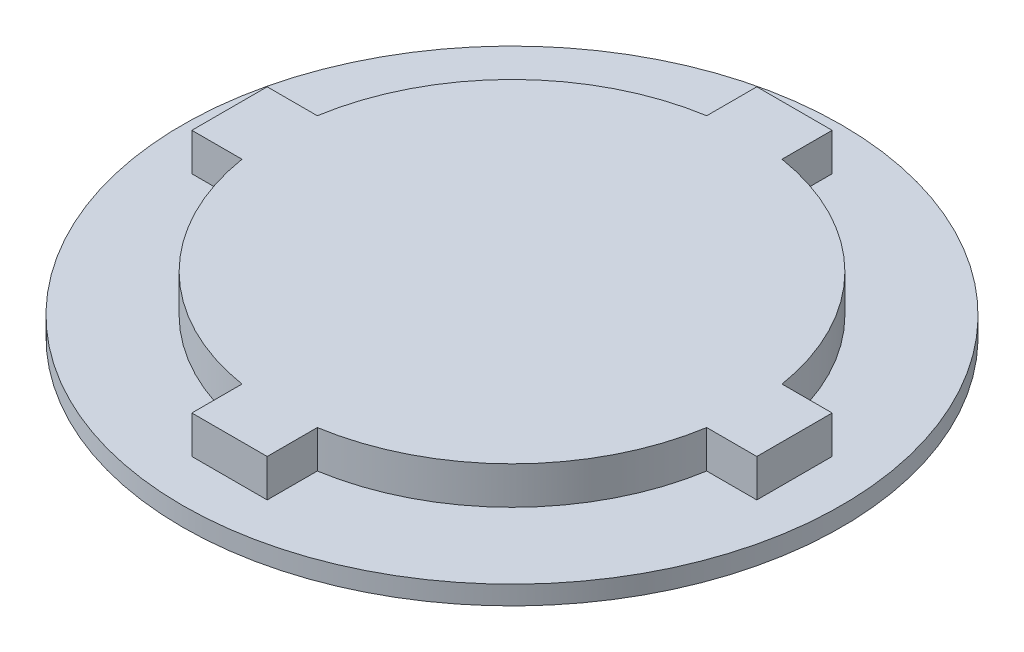
SolidWorks part; units mm, degrees
ref_plane "Alzado" through (0, 0, 0) normal (0, 0, 1) x (1, 0, 0)
ref_plane "Planta" through (0, 0, 0) normal (0, 1, 0) x (1, 0, 0)
ref_plane "Vista lateral" through (0, 0, 0) normal (1, 0, 0) x (0, 0, -1)
sketch "Croquis5" plane through (0, 0, 0) normal (0, 1, 0) x (1, 0, 0)
  circle A0 centre (0, 0) radius 25
  dimension "D1" = 50
extrude "Saliente-Extruir3" add sketch "Croquis5" along normal blind 4
sketch "Croquis6" plane through (0, 0, 0) normal (0, -1, 0) x (1, 0, 0)
  line L0 (4, -30) -> (-4, -30)
  line L1 (30, 4) -> (-30, 4)
  line L2 (30, 4) -> (30, -4)
  line L3 (30, -4) -> (-30, -4)
  line L4 (-30, 4) -> (-30, -4)
  line L5 (30, 4) -> (-30, -4) construction
  line L6 (30, -4) -> (-30, 4) construction
  line L7 (4, -30) -> (4, 30)
  line L8 (4, 30) -> (-4, 30)
  line L9 (-4, -30) -> (-4, 30)
  point P0 (0, 0)
  point P13 (0, 0)
  circle M5 centre (0, 0) radius 25
  dimension "D1" = 60
  dimension "D2" = 8
  dimension "D3" = 2
extrude "Saliente-Extruir4" add sketch "Croquis6" against normal blind 4 contours L1 L4 L3 M5 | L9 L0 L7 M5 | L3 L2 L1 M5 | L9 L7 L8 M5 region at (0, 0, -27.4456) region at (27.4456, 0, 0) region at (-27.4456, 0, 0) region at (0, 0, 27.4456)
sketch "Croquis7" plane through (0, 0, 0) normal (0, -1, 0) x (1, 0, 0)
  circle A0 centre (0, 0) radius 35
  dimension "D1" = 70
extrude "Saliente-Extruir5" add sketch "Croquis7" along normal blind 2
